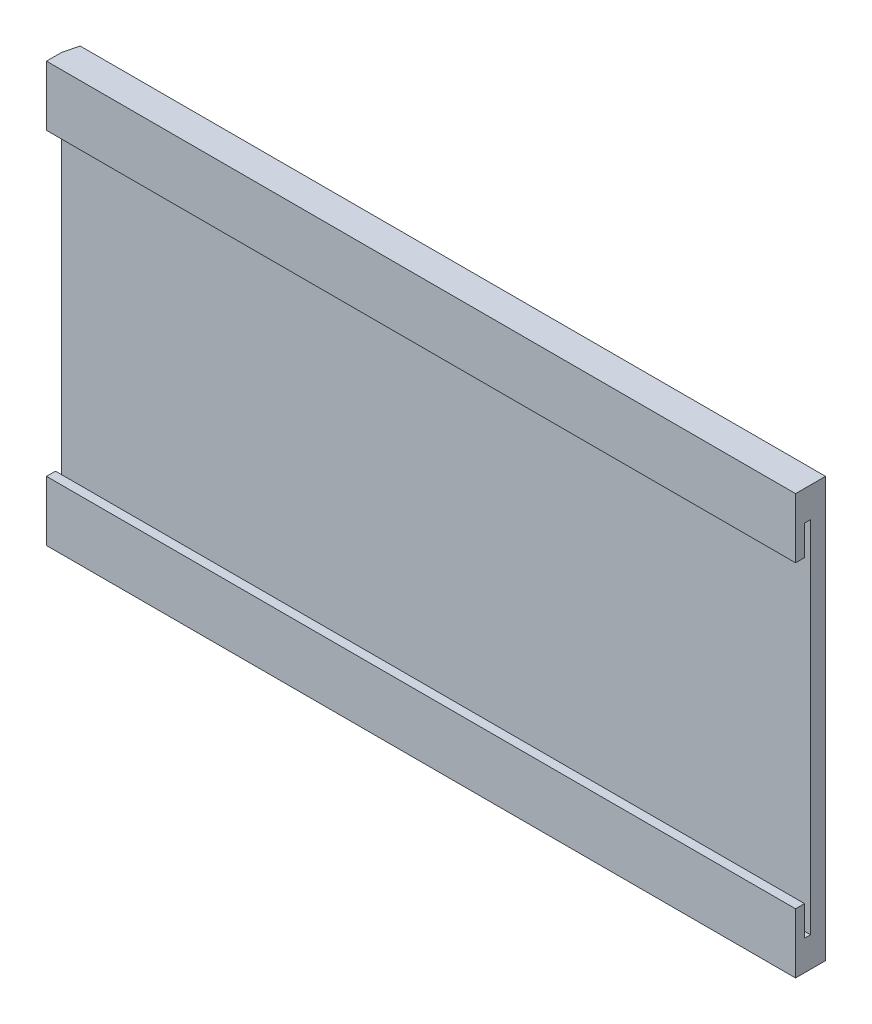
SolidWorks part; units mm, degrees
ref_plane "Front Plane" through (0, 0, 0) normal (0, 0, 1) x (1, 0, 0)
ref_plane "Top Plane" through (0, 0, 0) normal (0, 1, 0) x (1, 0, 0)
ref_plane "Right Plane" through (0, 0, 0) normal (1, 0, 0) x (0, 0, -1)
sketch "Sketch1" plane through (0, 0, 0) normal (0, 0, 1) x (1, 0, 0)
  line L0 (0, 60) -> (250, 60)
  line L1 (0, 70) -> (250, 70)
  line L2 (0, 70) -> (0, -70)
  line L3 (0, -70) -> (250, -70)
  line L4 (250, 70) -> (250, -70)
  line L5 (0, 50) -> (250, 50)
  line L6 (0, -60) -> (250, -60)
  line L7 (0, -50) -> (250, -50)
  line L8 (0, 0) -> (250, 0) construction
  line L9 (0, 0) -> (250, 0) construction
  dimension "D1" = 140
  dimension "D3" = 20
  dimension "D4" = 10
  dimension "D5" = 20
  dimension "D6" = 10
extrude "Boss-Extrude1" add sketch "Sketch1" along normal blind 5 and the other way blind 5 contours L2 L5 L4 L0 | L4 L1 L2 L0 | L7 L2 L6 L4 | L6 L2 L3 L4 | L2 L7 L4 L5 | L2 L1 L4 L3 region at (125, 65, 0) region at (125, 55, 0) region at (125, 0, 0) region at (125, -55, 0) region at (125, -65, 0)
extrude "Cut-Extrude1" cut sketch "Sketch1<3>" along normal through all contours L2 L7 L4 L5 | L2 L9 L4 L5 region at (125, 25, 0) region at (125, -25, 0)
sketch "Sketch1<3>" plane through (0, 0, 0) normal (0, 0, 1) x (1, 0, 0) same geometry as "Sketch1"
extrude "Cut-Extrude2" cut sketch "Sketch1<4>" along normal blind 2 contours L2 L5 L4 L0 | L7 L2 L6 L4 region at (125, 55, 0) region at (125, -55, 0)
sketch "Sketch1<4>" plane through (0, 0, 0) normal (0, 0, 1) x (1, 0, 0) same geometry as "Sketch1"
sketch "Sketch2" plane through (0, 0, 0) normal (0, 1, 0) x (1, 0, 0)
  line L0 (0, 0) -> (7.5, 30)
  line L3 (7.5, 30) -> (0, 30)
  line L5 (0, 30) -> (0, 0)
  dimension "D1" = 7.5
  dimension "D2" = 30
  dimension "D3" = 5
extrude "Cut-Extrude3" cut sketch "Sketch2" against normal through all both and the other way through all
